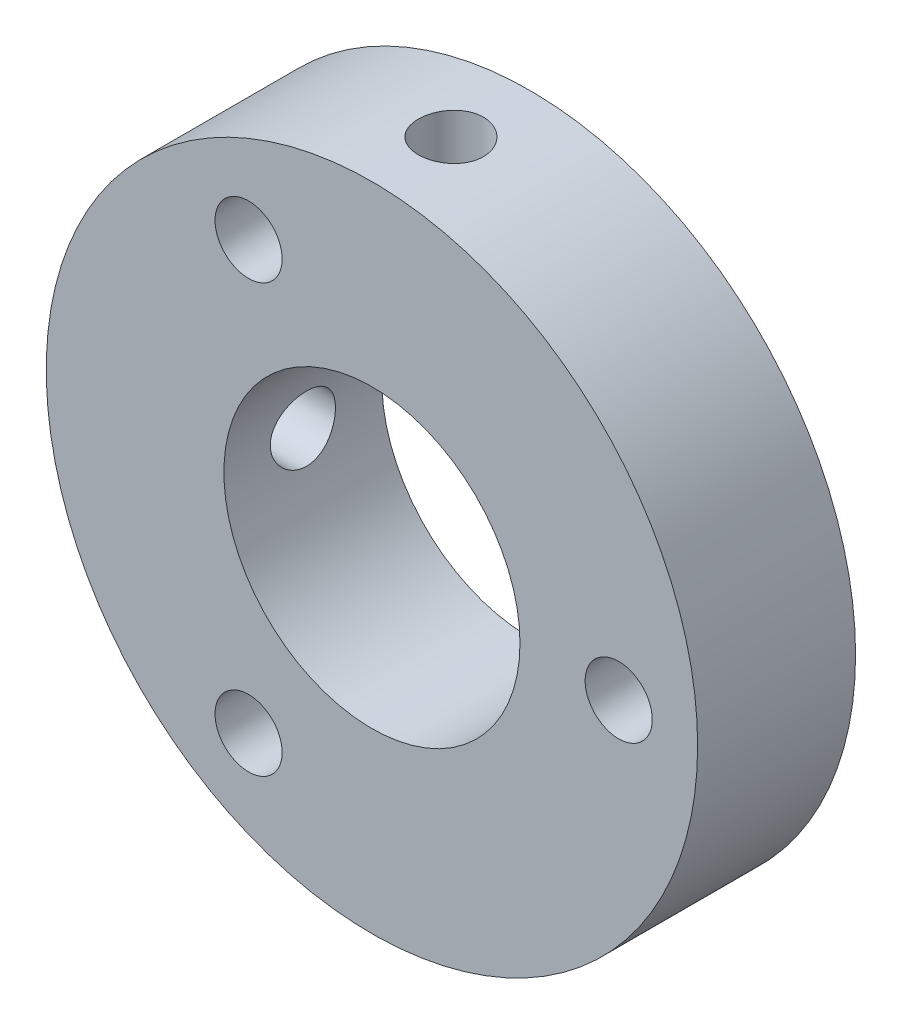
SolidWorks part; units mm, degrees
material "Сплав 2024"
ref_plane "Спереди" through (0, 0, 0) normal (0, 0, 1) x (1, 0, 0)
ref_plane "Сверху" through (0, 0, 0) normal (0, 1, 0) x (1, 0, 0)
ref_plane "Справа" through (0, 0, 0) normal (1, 0, 0) x (0, 0, -1)
sketch "Эскиз1" plane through (0, 0, 0) normal (0, 0, 1) x (1, 0, 0)
  circle A0 centre (0, 0) radius 16.5
  circle A1 centre (0, 0) radius 7.5
  dimension "D1" = 33
  dimension "D2" = 15
extrude "Бобышка-Вытянуть1" add sketch "Эскиз1" along normal blind 8
sketch "Эскиз2" plane through (0, 0, 8) normal (0, 0, 1) x (1, 0, 0)
  line L0 (0, 0) -> (20.3112, 0) construction
  line L1 (0, 0) -> (-10.9456, 18.9584) construction
  line L2 (0, 0) -> (-9.5861, -16.6035) construction
  circle A0 centre (0, 0) radius 12.5 construction
  point P3 (-6.25, 10.8253)
  point P7 (12.5, 0)
  point P8 (-6.25, -10.8253)
  dimension "D1" = 25
  dimension "D2" = 120
  dimension "D3" = 120
hole_wizard "Отверстие с зазором M31" positions "Эскиз4" profile "Эскиз3" hole size "M3" standard "Ansi Metric" end condition through all
sketch "Эскиз4" plane through (0, 0, 8) normal (0, 0, 1) x (1, 0, 0)
  point P0 (-6.25, 10.8253)
  point P3 (12.5, 0)
  point P6 (-6.25, -10.8253)
sketch "Эскиз3" plane through (-6.25, 10.8253, 8) normal (1, 0, 0) x (0, -1, 0)
  line L0 (0, 0) -> (0, 8)
  line L1 (0, 8) -> (1.7, 8)
  line L2 (1.7, 8) -> (1.7, 0)
  line L5 (1.7, 0) -> (0, 0)
  line L11 (0, -6.35) -> (0, 107.95) construction
  dimension "Диаметр сквозного отверстия" = 3.4
  dimension "Глубина сквозного отверстия" = 8
ref_plane "Плоскость1" through (-16.5, 0, 0) normal (-1, 0, 0) x (0, 0, 1)
sketch "Эскиз5" plane through (-16.5, 0, 0) normal (-1, 0, 0) x (0, 0, 1)
  line L0 (4, 16.5) -> (4, -16.5) construction
  line L1 (8, 16.5) -> (0, 16.5) construction
  line L2 (0, -16.5) -> (8, -16.5) construction
  line L3 (0, 0) -> (8, 0) construction
  line L4 (8, -16.5) -> (8, 16.5) construction
hole_wizard "Отверстие обработанное метчиком M4x0.71" positions "Эскиз7" profile "Эскиз6" tap size "M4x0.7" standard "Ansi Metric" end condition up to next
sketch "Эскиз7" plane through (-16.5, 0, 0) normal (-1, 0, 0) x (0, 0, 1)
  line L0 (4, 16.5) -> (4, -16.5) construction
  point P0 (4, 0)
sketch "Эскиз6" plane through (-16.5, 0, 4) normal (0, 1, 0) x (0, 0, 1)
  line L0 (0, 0) -> (0, 9)
  line L1 (0, 9) -> (1.65, 9)
  line L2 (1.65, 9) -> (1.65, 0)
  line L5 (1.65, 0) -> (0, 0)
  line L11 (0, -6.35) -> (0, 107.95) construction
  dimension "Диаметр проходного сверла" = 3.3
  dimension "Глубина проходного сверла" = 9
cosmetic thread "Отверстие резьбы1" parameters "D2"=4
ref_plane "Плоскость2" through (0, 16.5, 0) normal (0, 1, 0) x (0, 0, 1)
sketch "Эскиз8" plane through (0, 16.5, 0) normal (0, 1, 0) x (0, 0, 1)
  line L0 (4, 16.5) -> (4, -16.5) construction
  line L1 (8, 16.5) -> (0, 16.5) construction
  line L2 (-5.5, -16.5) -> (5.5, -16.5) construction
  line L3 (8, 0) -> (0, 0) construction
  line L4 (8, -16.5) -> (8, 16.5) construction
  line L5 (0, 16.5) -> (0, -16.5) construction
hole_wizard "Отверстие обработанное метчиком M4x0.72" positions "Эскиз10" profile "Эскиз9" tap size "M4x0.7" standard "Ansi Metric" end condition up to next
sketch "Эскиз10" plane through (0, 16.5, 0) normal (0, 1, 0) x (0, 0, 1)
  line L0 (4, 16.5) -> (4, -16.5) construction
  point P0 (4, 0)
sketch "Эскиз9" plane through (0, 16.5, 4) normal (1, 0, 0) x (0, 0, 1)
  line L0 (0, 0) -> (0, 9)
  line L1 (0, 9) -> (1.65, 9)
  line L2 (1.65, 9) -> (1.65, 0)
  line L5 (1.65, 0) -> (0, 0)
  line L11 (0, -6.35) -> (0, 107.95) construction
  dimension "Диаметр проходного сверла" = 3.3
  dimension "Глубина проходного сверла" = 9
cosmetic thread "Отверстие резьбы2" parameters "D2"=4
